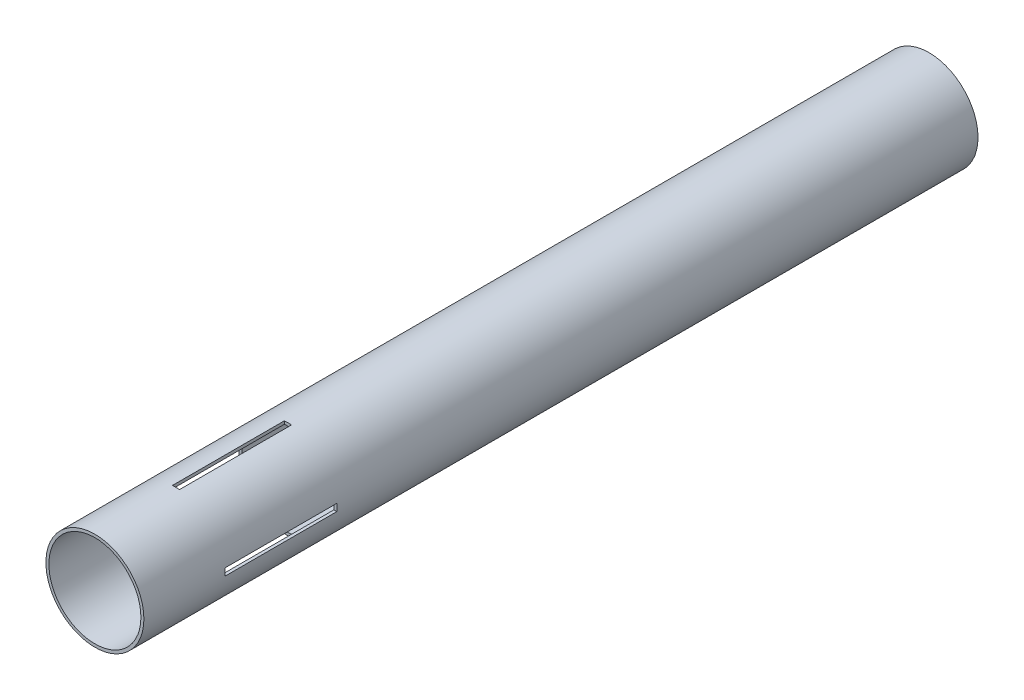
SolidWorks part; units mm, degrees
ref_plane "Front Plane" through (0, 0, 0) normal (0, 0, 1) x (1, 0, 0)
ref_plane "Top Plane" through (0, 0, 0) normal (0, 1, 0) x (1, 0, 0)
ref_plane "Right Plane" through (0, 0, 0) normal (1, 0, 0) x (0, 0, -1)
sketch "Sketch1" plane through (0, 0, 0) normal (0, 0, 1) x (1, 0, 0)
  circle A0 centre (0, 0) radius 20.555
  circle A1 centre (0, 0) radius 19.305
  dimension "D1" = 41.11
  dimension "D2" = 38.61
extrude "Boss-Extrude3" add sketch "Sketch1" against normal blind 350
ref_axis "Axis1" through (0, 0, -350) along (0, 0, 1)
sketch "Sketch2" plane through (0, 0, 0) normal (1, 0, 0) x (0, 0, -1)
  line L1 (34, 20.555) -> (81, 20.555)
  line L3 (34, 18.555) -> (81, 18.555)
  line L4 (81, 20.555) -> (81, 18.555)
  line L5 (0, 0) -> (47.1145, 0) construction
  line L6 (350, 0) -> (0, 0) construction
  line L7 (34, 20.555) -> (34, 18.555)
  line L8 (0, 20.555) -> (0, -20.555) construction
  dimension "D1" = 20.555
  dimension "D2" = 2
  dimension "D3" = 34
  dimension "D4" = 47
extrude "Cut-Extrude1" cut sketch "Sketch2" against normal mid plane 3 contours L1 L4 L3 L7
pattern_circular "CirPattern1" count 4 over 360 about axis through (0, 0, -350) along (0, 0, 1) of "Cut-Extrude1"
